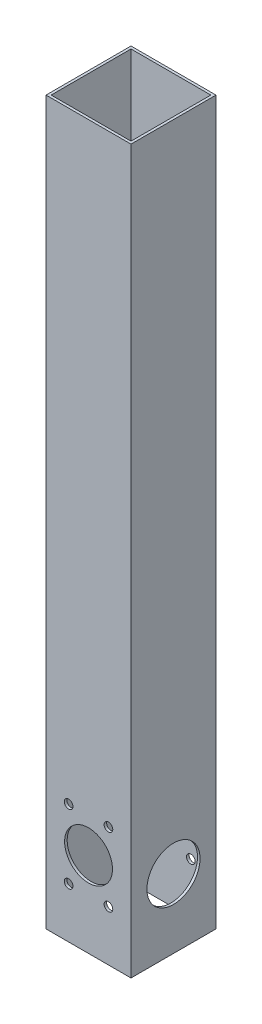
SolidWorks part; units mm, degrees
material "6061 Alloy"
ref_plane "Front Plane" through (0, 0, 0) normal (0, 0, 1) x (1, 0, 0)
ref_plane "Top Plane" through (0, 0, 0) normal (0, 1, 0) x (1, 0, 0)
ref_plane "Right Plane" through (0, 0, 0) normal (1, 0, 0) x (0, 0, -1)
sketch "Sketch1" plane through (0, 0, 0) normal (0, 1, 0) x (1, 0, 0)
  line L1 (25.4, 25.4) -> (-25.4, 25.4)
  line L2 (25.4, 25.4) -> (25.4, -25.4)
  line L3 (25.4, -25.4) -> (-25.4, -25.4)
  line L4 (-25.4, 25.4) -> (-25.4, -25.4)
  line L5 (25.4, 25.4) -> (-25.4, -25.4) construction
  line L6 (25.4, -25.4) -> (-25.4, 25.4) construction
  point P0 (0, 0)
  dimension "D1" = 50.8
extrude "Extrude-Thin1" add sketch "Sketch1" along normal blind 431.8 thin thin type one direction reverse wall 1.524
sketch "Sketch2" plane through (0, 0, 0) normal (0, 0, 1) x (1, 0, 0)
  line L0 (-36.2563, 68.2625) -> (38.5702, 68.2625) construction
  line L1 (-25.4, 0) -> (25.4, 0) construction
  line L2 (-25.4, 50.8) -> (25.4, 50.8) construction
  line L6 (25.4, 431.8) -> (25.4, 0) construction
  line L7 (-25.4, 431.8) -> (-25.4, 0) construction
  line L8 (-11.9062, 30.1778) -> (11.9063, 30.1778) construction
  line L9 (-11.9062, 71.4222) -> (11.9063, 71.4222) construction
  circle A0 centre (0, 50.8) radius 14.3002
  circle A1 centre (0, 50.8) radius 23.8125 construction
  circle A2 centre (-11.9062, 30.1778) radius 2.5908
  circle A3 centre (11.9063, 30.1778) radius 2.5908
  circle A4 centre (11.9063, 71.4222) radius 2.5908
  circle A5 centre (-11.9062, 71.4222) radius 2.5908
  point P11 (0, 50.8)
  dimension "D1" = 28.6004
  dimension "D3" = 17.4625
  dimension "D4" = 47.625
  dimension "D6" = 5.1816
  dimension "D2" = 50.8
  dimension "D5" = 60
extrude "Cut-Extrude1" cut sketch "Sketch2" along normal through all both and the other way through all
sketch "Sketch3" plane through (25.4, 0, 0) normal (1, 0, 0) x (0, 0, -1)
  line L0 (-25.4, 50.8) -> (25.4, 50.8) construction
  line L1 (-25.4, 65.1002) -> (-25.4, 36.4998) construction
  line L3 (25.4, 431.8) -> (25.4, 0) construction
  circle A0 centre (0, 41.275) radius 15.875
  point P4 (0, 0)
  point P7 (-9.8037, 42.3263)
  point P8 (0, 0)
  point P9 (0, 50.8)
  point P10 (0, 30.3644)
  dimension "D1" = 31.75
  dimension "D2" = 9.525
extrude "Cut-Extrude2" cut sketch "Sketch3" against normal up to surface (1.524 mm away) up to face at (23.876, 215.9, 0)
